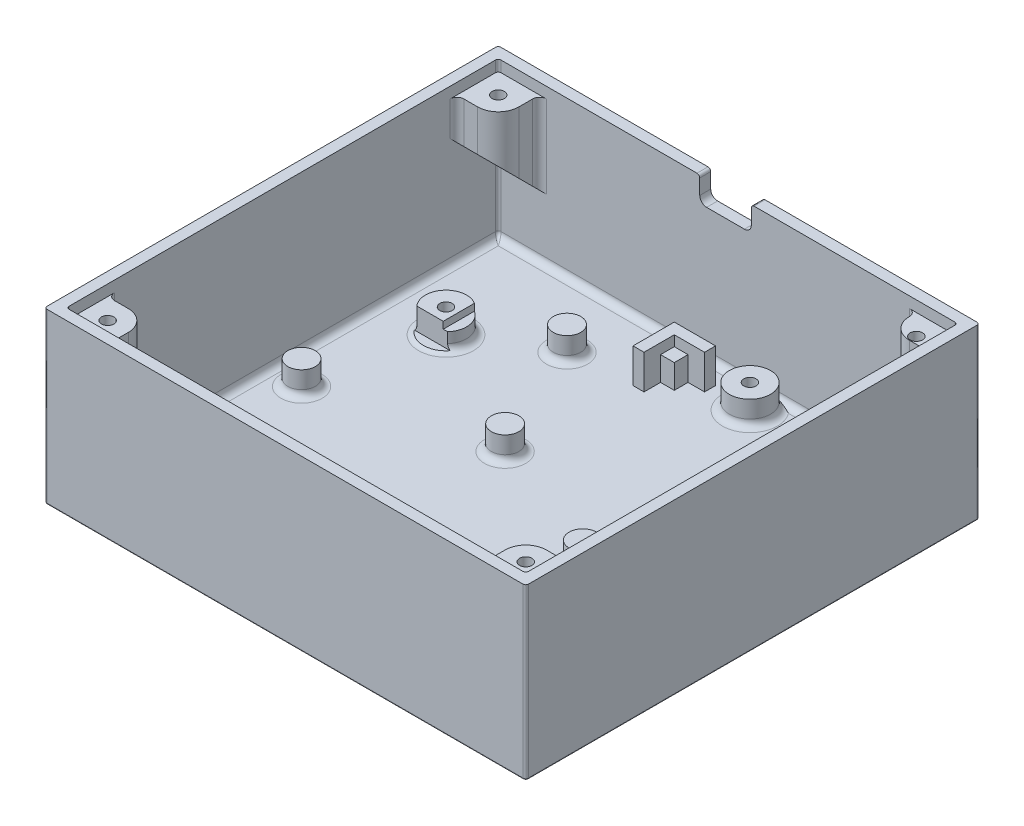
SolidWorks part; units mm, degrees
ref_plane "前视基准面" through (0, 0, 0) normal (0, 0, 1) x (1, 0, 0)
ref_plane "上视基准面" through (0, 0, 0) normal (0, 1, 0) x (1, 0, 0)
ref_plane "右视基准面" through (0, 0, 0) normal (1, 0, 0) x (0, 0, -1)
other "Configuration Table"
sketch "草图1" plane through (0, 0, 0) normal (0, 1, 0) x (1, 0, 0)
  line L1 (0, 0) -> (70, 0)
  line L2 (0, 0) -> (0, 66)
  line L3 (0, 66) -> (70, 66)
  line L4 (70, 0) -> (70, 66)
  dimension "D1" = 70
  dimension "D2" = 66
extrude "凸台-拉伸1" add sketch "草图1" along normal blind 2
sketch "草图2" plane through (0, 2, 0) normal (0, 1, 0) x (1, 0, 0)
  line L0 (70, 0) -> (70, 66) construction
  line L1 (66.8, 60) -> (31.6, 60)
  line L2 (66.8, 60) -> (66.8, 6)
  line L3 (66.8, 6) -> (31.6, 6)
  line L4 (31.6, 60) -> (31.6, 6)
  line L5 (70, 66) -> (0, 66) construction
  line L11 (68.4, 61.6) -> (30, 61.6)
  line L12 (30, 61.6) -> (30, 4.4)
  line L13 (68.4, 4.4) -> (30, 4.4)
  line L14 (68.4, 61.6) -> (68.4, 4.4)
  dimension "D1" = 35.2
  dimension "D2" = 54
  dimension "D3" = 3.2
  dimension "D4" = 6
  dimension "D5" = 1.6
extrude "凸台-拉伸2" add sketch "草图2" along normal blind 5
sketch "草图3" plane through (0, 2, 0) normal (0, 1, 0) x (1, 0, 0)
  line L0 (31.6, 6) -> (66.8, 6) construction
  line L1 (31.6, 60) -> (33.6, 60)
  line L2 (31.6, 60) -> (31.6, 58)
  line L3 (31.6, 58) -> (33.6, 58)
  line L4 (33.6, 60) -> (33.6, 58)
  line L5 (66.8, 60) -> (64.8, 60)
  line L6 (66.8, 60) -> (66.8, 58)
  line L7 (66.8, 58) -> (64.8, 58)
  line L8 (64.8, 60) -> (64.8, 58)
  line L9 (31.6, 6) -> (33.6, 6)
  line L10 (31.6, 6) -> (31.6, 8)
  line L11 (31.6, 8) -> (33.6, 8)
  line L12 (33.6, 6) -> (33.6, 8)
  line L13 (66.8, 6) -> (64.8, 6)
  line L14 (66.8, 6) -> (66.8, 8)
  line L15 (66.8, 8) -> (64.8, 8)
  line L16 (64.8, 6) -> (64.8, 8)
  line L17 (66.8, 6) -> (66.8, 60) construction
  circle A0 centre (49.3, 29) radius 2
  dimension "D9" = 4
  dimension "D11" = 17.5
  dimension "D1" = 2
  dimension "D2" = 2
  dimension "D3" = 2
  dimension "D4" = 2
  dimension "D5" = 2
  dimension "D6" = 2
  dimension "D7" = 2
  dimension "D8" = 2
  dimension "D10" = 23
extrude "凸台-拉伸3" add sketch "草图3" along normal blind 3.5
sketch "草图4" plane through (0, 7, 0) normal (0, 1, 0) x (1, 0, 0)
  line L0 (68.4, 61.6) -> (30, 61.6) construction
  line L1 (36, 61.6) -> (62.4, 61.6)
  line L2 (36, 61.6) -> (36, 60)
  line L3 (36, 60) -> (62.4, 60)
  line L4 (62.4, 61.6) -> (62.4, 60)
  line L5 (64.8, 60) -> (33.6, 60) construction
  line L6 (30, 61.6) -> (30, 4.4) construction
  line L7 (30, 55.6) -> (31.6, 55.6)
  line L8 (30, 55.6) -> (30, 10.4)
  line L9 (30, 10.4) -> (31.6, 10.4)
  line L10 (31.6, 55.6) -> (31.6, 10.4)
  line L11 (31.6, 58) -> (31.6, 8) construction
  line L12 (31.6, 6) -> (66.8, 6) construction
  line L13 (36, 6) -> (62.4, 6)
  line L14 (36, 6) -> (36, 4.4)
  line L15 (36, 4.4) -> (62.4, 4.4)
  line L16 (62.4, 6) -> (62.4, 4.4)
  line L17 (30, 4.4) -> (68.4, 4.4) construction
  line L18 (30, 61.6) -> (30, 4.4) construction
  line L19 (68.4, 4.4) -> (68.4, 61.6) construction
  line L20 (66.8, 6) -> (66.8, 60) construction
  line L21 (66.8, 55.6) -> (68.4, 55.6)
  line L22 (66.8, 55.6) -> (66.8, 10.4)
  line L23 (66.8, 10.4) -> (68.4, 10.4)
  line L24 (68.4, 55.6) -> (68.4, 10.4)
  line L25 (68.4, 61.6) -> (30, 61.6) construction
  dimension "D1" = 6
  dimension "D2" = 6
  dimension "D3" = 6
  dimension "D4" = 6
  dimension "D5" = 6
  dimension "D6" = 6
  dimension "D7" = 6
  dimension "D8" = 6
extrude "切除-拉伸1" cut sketch "草图4" against normal up to surface (5 mm away) up to face at (35, 2, -33)
sketch "草图7" plane through (0, 2, 0) normal (0, 1, 0) x (1, 0, 0)
  line L0 (30, 4.4) -> (36, 4.4) construction
  line L2 (30, 10.4) -> (30, 4.4) construction
  circle A3 centre (6, 31.4) radius 2
  dimension "D1" = 27
  dimension "D7" = 4
  dimension "D9" = 24
extrude "凸台-拉伸5" add sketch "草图7" along normal blind 3.5
sketch "草图8" plane through (0, 2, 0) normal (0, 1, 0) x (1, 0, 0)
  line L0 (70, 66) -> (0, 66) construction
  line L1 (30, 10.4) -> (30, 4.4) construction
  line L2 (30, 61.6) -> (30, 55.6) construction
  line L3 (30, 4.4) -> (36, 4.4) construction
  line L4 (36, 61.6) -> (30, 61.6) construction
  line L5 (68.4, 4.4) -> (68.4, 10.4) construction
  line L6 (62.4, 6) -> (66.8, 6) construction
  line L8 (31.6, 60) -> (31.6, 55.6) construction
  line L9 (36, 60) -> (31.6, 60) construction
  circle A1 centre (10, 48.4) radius 3
  circle A3 centre (10, 10.4) radius 2
  circle A5 centre (24.4, 13.1) radius 3
  circle A6 centre (29, 38) radius 2
  circle A7 centre (21, 55) radius 2
  circle A8 centre (49.4, 5) radius 3
  circle A9 centre (41.6, 61) radius 3
  dimension "D3" = 1
  dimension "D4" = 6
  dimension "D7" = 4
  dimension "D8" = 20
  dimension "D9" = 6
  dimension "D10" = 6
  dimension "D11" = 5.6
  dimension "D12" = 8.7
  dimension "D13" = 4
  dimension "D14" = 4
  dimension "D16" = 11
  dimension "D5" = 20
  dimension "D6" = 13.2
  dimension "D17" = 6
  dimension "D18" = 19
  dimension "D19" = 1
  dimension "D20" = 6
  dimension "D21" = 10
  dimension "D22" = 1
  dimension "D23" = 9
  dimension "0" = 28
extrude "凸台-拉伸9" add sketch "草图8" along normal blind 3.5
sketch "草图9" plane through (0, 2, 0) normal (0, 1, 0) x (1, 0, 0)
  line L0 (1.6, 64.4) -> (1.6, 1.6)
  line L1 (0, 66) -> (70, 66)
  line L2 (0, 66) -> (0, 0)
  line L3 (0, 0) -> (70, 0)
  line L4 (70, 66) -> (70, 0)
  line L5 (1.6, 1.6) -> (68.4, 1.6)
  line L6 (68.4, 64.4) -> (68.4, 1.6)
  line L7 (1.6, 64.4) -> (68.4, 64.4)
  line L8 (70, 0) -> (70, 66) construction
  line L9 (0, 0) -> (70, 0) construction
  dimension "D2" = 0
  dimension "D3" = 0
  dimension "D1" = 1.6
extrude "凸台-拉伸13" add sketch "草图9" along normal blind 21
sketch "草图10" plane through (0, 5.5, 0) normal (0, 1, 0) x (1, 0, 0)
  circle A0 centre (10, 48.4) radius 0.9
  circle A2 centre (24.4, 13.1) radius 0.9
  circle A3 centre (41.6, 61) radius 0.9
  circle A4 centre (49.4, 5) radius 0.9
  dimension "D1" = 1.8
  dimension "D3" = 1.8
  dimension "D4" = 1.8
  dimension "D5" = 1.8
extrude "切除-拉伸2" cut sketch "草图10" against normal blind 5
sketch "草图11" plane through (0, 23, 0) normal (0, 1, 0) x (1, 0, 0)
  line L0 (68.4, 64.4) -> (1.6, 64.4) construction
  line L1 (68.4, 64.4) -> (62.4, 64.4)
  line L2 (68.4, 64.4) -> (68.4, 60.4)
  line L3 (68.4, 60.4) -> (62.4, 60.4)
  line L4 (62.4, 64.4) -> (62.4, 60.4)
  line L5 (68.4, 61.6) -> (68.4, 64.4) construction
  line L7 (68.4, 1.6) -> (62.4, 1.6)
  line L8 (68.4, 1.6) -> (68.4, 7.6)
  line L9 (68.4, 7.6) -> (62.4, 7.6)
  line L10 (62.4, 1.6) -> (62.4, 7.6)
  line L11 (1.6, 1.6) -> (7.6, 1.6)
  line L12 (1.6, 1.6) -> (1.6, 7.6)
  line L13 (1.6, 7.6) -> (7.6, 7.6)
  line L14 (7.6, 1.6) -> (7.6, 7.6)
  line L15 (1.6, 64.4) -> (7.6, 64.4)
  line L16 (1.6, 64.4) -> (1.6, 58.4)
  line L17 (1.6, 58.4) -> (7.6, 58.4)
  line L18 (7.6, 64.4) -> (7.6, 58.4)
  dimension "D1" = 4
  dimension "D2" = 6
  dimension "D3" = 6
  dimension "D4" = 6
  dimension "D5" = 6
  dimension "D6" = 6
  dimension "D7" = 6
  dimension "D8" = 6
extrude "凸台-拉伸14" add sketch "草图11" against normal blind 6
chamfer "倒角1" distance 6 angle 45 4 edges at (65.4, 17, -64.4) (4.6, 17, -64.4) (65.4, 17, -1.6) (4.6, 17, -1.6)
sketch "草图12" plane through (0, 23, 0) normal (0, 1, 0) x (1, 0, 0)
  line L0 (1.6, 64.4) -> (1.6, 1.6)
  line L1 (0, 66) -> (70, 66)
  line L2 (0, 66) -> (0, 0)
  line L3 (0, 0) -> (70, 0)
  line L4 (70, 66) -> (70, 0)
  line L5 (1.6, 1.6) -> (68.4, 1.6)
  line L6 (68.4, 64.4) -> (68.4, 1.6)
  line L7 (1.6, 64.4) -> (68.4, 64.4)
  dimension "D1" = 1.6
extrude "凸台-拉伸15" add sketch "草图12" along normal blind 1.6
sketch "草图13" plane through (0, 23, 0) normal (0, 1, 0) x (1, 0, 0)
  line L0 (1.6, 58.4) -> (7.6, 58.4) construction
  line L1 (7.6, 58.4) -> (7.6, 64.4) construction
  circle A0 centre (4.6, 61.4) radius 0.9
  circle A1 centre (65.4, 61.4) radius 0.9
  circle A2 centre (65.4, 4.6) radius 0.9
  circle A3 centre (4.6, 4.6) radius 0.9
  dimension "D1" = 1.8
  dimension "D2" = 3
  dimension "D3" = 3
  dimension "D4" = 2
  dimension "D5" = 2
extrude "切除-拉伸3" cut sketch "草图13" against normal blind 6
sketch "草图14" plane through (0, 0, -64.4) normal (0, 0, 1) x (1, 0, 0)
  line L1 (30.9, 24.6) -> (38.4, 24.6)
  line L2 (30.9, 24.6) -> (30.9, 21)
  line L3 (30.9, 21) -> (38.4, 21)
  line L4 (38.4, 24.6) -> (38.4, 21)
  line L5 (68.4, 24.6) -> (1.6, 24.6) construction
  dimension "D1" = 3.6
  dimension "D2" = 7.5
  dimension "D3" = 0
  dimension "D4" = 30
extrude "切除-拉伸4" cut sketch "草图14" against normal blind 6
fillet "圆角1" radius 1 37 edges at (33.6, 2, -7) (32.6, 2, -8) (31.6, 2, -9.2) (30.8, 2, -10.4) (30, 2, -7.4) (33, 2, -4.4) (36, 2, -5.2) (34.8, 2, -6) (6, 2, -33.4) (10, 2, -51.4) (10, 2, -12.4) (24.4, 2, -16.1) (49.4, 2, -8) (41.6, 2, -64) (49.3, 2, -31) (21, 2, -57) (29, 2, -40) (65.4, 2, -4.4) (62.4, 2, -5.2) (63.6, 2, -6) (64.8, 2, -7) (65.8, 2, -8) (66.8, 2, -9.2) (67.6, 2, -10.4) (65.4, 2, -61.6) (67.6, 2, -55.6) (66.8, 2, -56.8) (65.8, 2, -58) (64.8, 2, -59) (63.6, 2, -60) (62.4, 2, -60.8) (35, 2, -64.4) (68.4, 2, -63) (68.4, 2, -33) (68.4, 2, -3) (35, 2, -1.6) (1.6, 2, -33)
fillet "圆角2" radius 1 2 edges at (38.4, 21, -65.2) (30.9, 21, -65.2)
fillet "圆角3" radius 3 4 edges at (7.6, 20, -7.6) (62.4, 20, -7.6) (62.4, 19, -60.4) (7.6, 20, -58.4)
fillet "圆角4" radius 1 8 edges at (1.6, 20, -7.6) (7.6, 17, -1.6) (62.4, 17, -1.6) (68.4, 20, -7.6) (68.4, 19, -60.4) (62.4, 17, -64.4) (1.6, 20, -58.4) (7.6, 17, -64.4)
fillet "圆角5" radius 0.4 18 edges at (68.1071, 2.2929, -64.1071) (1.8929, 2.2929, -64.1071) (1.8929, 2.2929, -1.8929) (68.1071, 2.2929, -1.8929) (68.4, 23.8, -1.6) (68.4, 7, -64.4) (68.4, 23.8, -64.4) (1.6, 23.8, -64.4) (1.6, 7, -64.4) (1.6, 23.8, -1.6) (1.6, 7, -1.6) (68.4, 7, -1.6) (0, 12.3, 0) (70, 12.3, 0) (70, 12.3, -66) (0, 12.3, -66) (30.9, 24.6, -65.2) (38.4, 24.6, -65.2)
fillet "圆角6" radius 0.2 8 edges at (69.8828, 0, -0.1172) (70, 0, -33) (69.8828, 0, -65.8828) (35, 0, -66) (0.1172, 0, -65.8828) (0, 0, -33) (0.1172, 0, -0.1172) (35, 0, 0)
sketch "草图16" plane through (0, 5.5, 0) normal (0, 1, 0) x (1, 0, 0)
  line L0 (19.6902, 11.5438) -> (27.1876, 17.2146)
  line L1 (27.1876, 17.2146) -> (20.443, 18.3402)
  line L2 (20.443, 18.3402) -> (19.6902, 11.5438)
  line L7 (11.6, 52.9816) -> (16.4202, 52.9816)
  line L8 (11.6, 52.9816) -> (11.6, 44.2642)
  line L9 (11.6, 44.2642) -> (16.4202, 44.2642)
  line L10 (16.4202, 52.9816) -> (16.4202, 44.2642)
  circle A0 centre (10, 48.4) radius 3 construction
  circle A1 centre (24.4, 13.1) radius 3 construction
  dimension "D1" = 1.6
  dimension "D2" = 1.6
extrude "切除-拉伸5" cut sketch "草图16" against normal blind 1
sketch "草图17" plane through (0, 5.5, 0) normal (0, 1, 0) x (1, 0, 0)
  line L0 (19.5348, 42.7321) -> (10.0877, 42.4653) construction
  line L1 (5.695, 46.4) -> (15.6469, 46.4)
  line L2 (5.695, 46.4) -> (5.695, 42.6223)
  line L3 (5.695, 42.6223) -> (15.6469, 42.6223)
  line L4 (15.6469, 46.4) -> (15.6469, 42.6223)
  arc A0 (11.6, 50.9377) -> (11.6, 45.8623) centre (10, 48.4) ccw construction
  dimension "D1" = 2
extrude "切除-拉伸6" cut sketch "草图17" against normal blind 3.2
